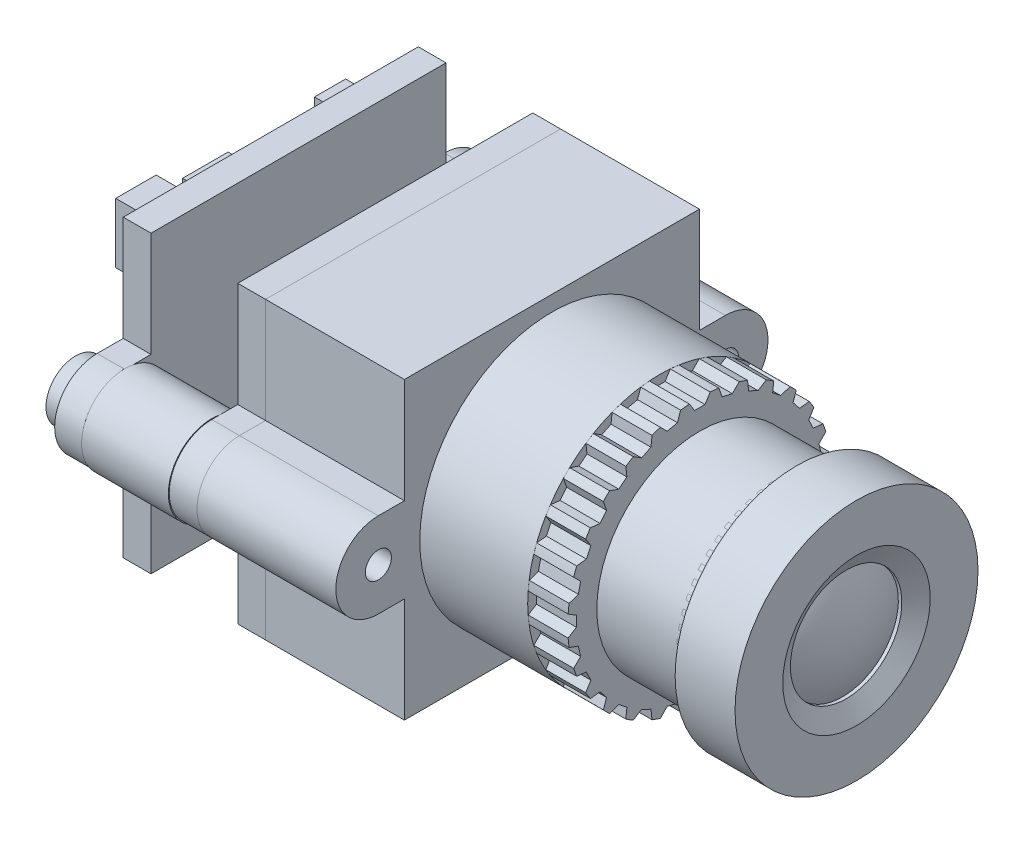
SolidWorks part; units mm, degrees
ref_plane "Front Plane" through (0, 0, 0) normal (0, 0, 1) x (1, 0, 0)
ref_plane "Top Plane" through (0, 0, 0) normal (0, 1, 0) x (1, 0, 0)
ref_plane "Right Plane" through (0, 0, 0) normal (1, 0, 0) x (0, 0, -1)
ref_axis "Axis1" through (-11.8965, 0, 0) along (1, 0, 0)
sketch "Sketch1" plane through (0, 0, 0) normal (1, 0, 0) x (0, 0, -1)
  circle A0 centre (0, 0) radius 7
  dimension "D1" = 14
extrude "Boss-Extrude1" add sketch "Sketch1" against normal blind 3.45
sketch "Sketch2" plane through (-3.45, 0, 0) normal (-1, 0, 0) x (0, 0, 1)
  circle A0 centre (0, 0) radius 5.935
  dimension "D1" = 11.87
extrude "Boss-Extrude2" add sketch "Sketch2" along normal blind 5.58
sketch "Sketch3" plane through (-9.03, 0, 0) normal (-1, 0, 0) x (0, 0, 1)
  circle A0 centre (0, 0) radius 7.61
  dimension "D1" = 15.22
extrude "Boss-Extrude3" add sketch "Sketch3" along normal blind 2.3
sketch "Sketch4" plane through (0, 0, 0) normal (0, 0, 1) x (1, 0, 0)
  line L0 (-3.45, 0) -> (0, 0) construction
  line L1 (-3.45, 5.935) -> (-3.45, -5.935) construction
  line L2 (0, -7) -> (0, 7) construction
  line L3 (0, 7) -> (-3.45, 7) construction
  line L4 (-0.6, 4.25) -> (0, 4.25)
  line L5 (-0.6, 4.25) -> (-0.6, -4.25)
  line L6 (-0.6, -4.25) -> (0, -4.25)
  line L7 (0, 4.25) -> (0, -4.25)
  line L8 (-0.6, 4.25) -> (0, -4.25) construction
  line L9 (-0.6, -4.25) -> (0, 4.25) construction
  line L10 (0, 4.25) -> (-0.6, 3.2108)
  line L11 (-0.8, 0) -> (-0.6, 3.2108) construction
  line L12 (-0.8, -3.2108) -> (-0.6, -3.2108)
  line L13 (-0.8, -3.2108) -> (-0.8, 3.2108)
  line L14 (-0.8, 3.2108) -> (-0.6, 3.2108)
  line L15 (-0.6, -3.2108) -> (-0.6, 3.2108)
  line L16 (-0.8, -3.2108) -> (-0.6, 3.2108) construction
  line L17 (-0.8, 3.2108) -> (-0.6, -3.2108) construction
  line L18 (-0.7, 1.6054) -> (0, 1.6054) construction
  line L19 (-0.8, 0) -> (0, 0)
  line L21 (0, 0) -> (0.6, 0)
  line L22 (0, 0) -> (0, 4.25)
  line L23 (0, 4.25) -> (0.6, 4.25)
  line L24 (0.6, 0) -> (0.6, 4.25)
  spline S0 degree 2 poles (0, 0) (0, 1.7034) (-0.8, 3.2108) knots 0 0 0 1 1 1
  point P6 (-0.3, 0)
  point P15 (-0.7, 0)
  dimension "D1" = 0.6
  dimension "D2" = 2.75
  dimension "D3" = 60
  dimension "D4" = 0.2
  dimension "D5" = 0.6
revolve "Cut-Revolve7" cut sketch "Sketch4" angle 360 about axis through (-11.8965, 0, 0) along (1, 0, 0) region at (0.3, 2.125, 0) region at (-0.2115, 2.72, 0) region at (-0.6658, 3.0768, 0)
sketch "Sketch5" plane through (-9.03, 0, 0) normal (1, 0, 0) x (0, 0, -1)
  line L0 (0, 7.61) -> (0, -7.61) construction
  line L1 (0.6, 7.5863) -> (0.3, 7.11)
  line L2 (0.3, 7.11) -> (-0.3, 7.11)
  line L3 (-0.6, 7.5863) -> (-0.3, 7.11)
  line L4 (2.2731, 7.2626) -> (1.8746, 6.865)
  line L5 (1.8746, 6.865) -> (1.2896, 6.9985)
  line L6 (1.1032, 7.5296) -> (1.2896, 6.9985)
  line L7 (3.8322, 6.5747) -> (3.3552, 6.2757)
  line L8 (3.3552, 6.2757) -> (2.8146, 6.5361)
  line L9 (2.751, 7.0954) -> (2.8146, 6.5361)
  line L10 (5.1991, 5.5571) -> (4.6676, 5.3718)
  line L11 (4.6676, 5.3718) -> (4.1985, 5.7459)
  line L12 (4.2609, 6.3053) -> (4.1985, 5.7459)
  line L13 (6.3053, 4.2609) -> (5.7459, 4.1985)
  line L14 (5.7459, 4.1985) -> (5.3718, 4.6676)
  line L15 (5.5571, 5.1991) -> (5.3718, 4.6676)
  line L16 (7.0954, 2.751) -> (6.5361, 2.8146)
  line L17 (6.5361, 2.8146) -> (6.2757, 3.3552)
  line L18 (6.5747, 3.8322) -> (6.2757, 3.3552)
  line L19 (7.5296, 1.1032) -> (6.9985, 1.2896)
  line L20 (6.9985, 1.2896) -> (6.865, 1.8746)
  line L21 (7.2626, 2.2731) -> (6.865, 1.8746)
  line L22 (7.5863, -0.6) -> (7.11, -0.3)
  line L23 (7.11, -0.3) -> (7.11, 0.3)
  line L24 (7.5863, 0.6) -> (7.11, 0.3)
  line L25 (7.2626, -2.2731) -> (6.865, -1.8746)
  line L26 (6.865, -1.8746) -> (6.9985, -1.2896)
  line L27 (7.5296, -1.1032) -> (6.9985, -1.2896)
  line L28 (6.5747, -3.8322) -> (6.2757, -3.3552)
  line L29 (6.2757, -3.3552) -> (6.5361, -2.8146)
  line L30 (7.0954, -2.751) -> (6.5361, -2.8146)
  line L31 (5.5571, -5.1991) -> (5.3718, -4.6676)
  line L32 (5.3718, -4.6676) -> (5.7459, -4.1985)
  line L33 (6.3053, -4.2609) -> (5.7459, -4.1985)
  line L34 (4.2609, -6.3053) -> (4.1985, -5.7459)
  line L35 (4.1985, -5.7459) -> (4.6676, -5.3718)
  line L36 (5.1991, -5.5571) -> (4.6676, -5.3718)
  line L37 (2.751, -7.0954) -> (2.8146, -6.5361)
  line L38 (2.8146, -6.5361) -> (3.3552, -6.2757)
  line L39 (3.8322, -6.5747) -> (3.3552, -6.2757)
  line L40 (1.1032, -7.5296) -> (1.2896, -6.9985)
  line L41 (1.2896, -6.9985) -> (1.8746, -6.865)
  line L42 (2.2731, -7.2626) -> (1.8746, -6.865)
  line L43 (-0.6, -7.5863) -> (-0.3, -7.11)
  line L44 (-0.3, -7.11) -> (0.3, -7.11)
  line L45 (0.6, -7.5863) -> (0.3, -7.11)
  line L46 (-2.2731, -7.2626) -> (-1.8746, -6.865)
  line L47 (-1.8746, -6.865) -> (-1.2896, -6.9985)
  line L48 (-1.1032, -7.5296) -> (-1.2896, -6.9985)
  line L49 (-3.8322, -6.5747) -> (-3.3552, -6.2757)
  line L50 (-3.3552, -6.2757) -> (-2.8146, -6.5361)
  line L51 (-2.751, -7.0954) -> (-2.8146, -6.5361)
  line L52 (-5.1991, -5.5571) -> (-4.6676, -5.3718)
  line L53 (-4.6676, -5.3718) -> (-4.1985, -5.7459)
  line L54 (-4.2609, -6.3053) -> (-4.1985, -5.7459)
  line L55 (-6.3053, -4.2609) -> (-5.7459, -4.1985)
  line L56 (-5.7459, -4.1985) -> (-5.3718, -4.6676)
  line L57 (-5.5571, -5.1991) -> (-5.3718, -4.6676)
  line L58 (-7.0954, -2.751) -> (-6.5361, -2.8146)
  line L59 (-6.5361, -2.8146) -> (-6.2757, -3.3552)
  line L60 (-6.5747, -3.8322) -> (-6.2757, -3.3552)
  line L61 (-7.5296, -1.1032) -> (-6.9985, -1.2896)
  line L62 (-6.9985, -1.2896) -> (-6.865, -1.8746)
  line L63 (-7.2626, -2.2731) -> (-6.865, -1.8746)
  line L64 (-7.5863, 0.6) -> (-7.11, 0.3)
  line L65 (-7.11, 0.3) -> (-7.11, -0.3)
  line L66 (-7.5863, -0.6) -> (-7.11, -0.3)
  line L67 (-7.2626, 2.2731) -> (-6.865, 1.8746)
  line L68 (-6.865, 1.8746) -> (-6.9985, 1.2896)
  line L69 (-7.5296, 1.1032) -> (-6.9985, 1.2896)
  line L70 (-6.5747, 3.8322) -> (-6.2757, 3.3552)
  line L71 (-6.2757, 3.3552) -> (-6.5361, 2.8146)
  line L72 (-7.0954, 2.751) -> (-6.5361, 2.8146)
  line L73 (-5.5571, 5.1991) -> (-5.3718, 4.6676)
  line L74 (-5.3718, 4.6676) -> (-5.7459, 4.1985)
  line L75 (-6.3053, 4.2609) -> (-5.7459, 4.1985)
  line L76 (-4.2609, 6.3053) -> (-4.1985, 5.7459)
  line L77 (-4.1985, 5.7459) -> (-4.6676, 5.3718)
  line L78 (-5.1991, 5.5571) -> (-4.6676, 5.3718)
  line L79 (-2.751, 7.0954) -> (-2.8146, 6.5361)
  line L80 (-2.8146, 6.5361) -> (-3.3552, 6.2757)
  line L81 (-3.8322, 6.5747) -> (-3.3552, 6.2757)
  line L82 (-1.1032, 7.5296) -> (-1.2896, 6.9985)
  line L83 (-1.2896, 6.9985) -> (-1.8746, 6.865)
  line L84 (-2.2731, 7.2626) -> (-1.8746, 6.865)
  circle A0 centre (0, 0) radius 7.61 construction
  circle A1 centre (0, 0) radius 7.61 construction
  circle A2 centre (0, 0) radius 7.61
  point P12 (0, 7.11)
  point P13 (0, 0)
  point P123 (0, 0)
  circle M6 centre (0, 0) radius 7.61
  dimension "D1" = 0.6
  dimension "D2" = 1.2
  dimension "D3" = 0.5
  dimension "D5" = 0.5063
  dimension "D4" = 28
extrude "Cut-Extrude1" cut sketch "Sketch5" against normal up to next (2.3 mm away) contours L9 L8 L7 M6 | L6 L5 L4 M6 | L0 L2 L1 M6 | L84 L83 L82 M6 | L0 A2 L3 L2 | L81 L80 L79 M6 | L78 L77 L76 M6 | L75 L74 L73 M6 | L72 L71 L70 M6 | L69 L68 L67 M6 | L66 L65 L64 M6 | L63 L62 L61 M6 | L60 L59 L58 M6 | L57 L56 L55 M6 | L51 L50 L49 M6 | L54 L53 L52 M6 | L48 L47 L46 M6 | L0 L44 L43 M6 | L44 L0 A2 L45 | L42 L41 L40 M6 | L39 L38 L37 M6 | L36 L35 L34 M6 | L33 L32 L31 M6 | L30 L29 L28 M6 | L27 L26 L25 M6 | L24 L23 L22 M6 | L21 L20 L19 M6 | L18 L17 L16 M6 | L15 L14 L13 M6 | L12 L11 L10 M6 region at (-9.03, 7.384, -0.233) region at (-9.03, 7.384, 0.233) region at (-9.03, -7.384, -0.233) region at (-9.03, -7.384, 0.233) region at (-9.03, 7.1989, -1.6431) region at (-9.03, 7.1989, 1.6431) region at (-9.03, 6.6527, -3.2038) region at (-9.03, 6.6527, 3.2038) region at (-9.03, -7.1989, 1.6431) region at (-9.03, -7.1989, -1.6431) region at (-9.03, 5.773, -4.6038) region at (-9.03, 5.773, 4.6038) region at (-9.03, -6.6527, 3.2038) region at (-9.03, -6.6527, -3.2038) region at (-9.03, 4.6038, -5.773) region at (-9.03, 4.6038, 5.773) region at (-9.03, -5.773, 4.6038) region at (-9.03, -5.773, -4.6038) region at (-9.03, 3.2038, -6.6527) region at (-9.03, 3.2038, 6.6527) region at (-9.03, -4.6038, 5.773) region at (-9.03, -4.6038, -5.773) region at (-9.03, 1.6431, -7.1989) region at (-9.03, 1.6431, 7.1989) region at (-9.03, -3.2038, 6.6527) region at (-9.03, -3.2038, -6.6527) region at (-9.03, 0, -7.384) region at (-9.03, 0, 7.384) region at (-9.03, -1.6431, 7.1989) region at (-9.03, -1.6431, -7.1989)
sketch "Sketch6" plane through (-11.33, 0, 0) normal (-1, 0, 0) x (0, 0, 1)
  line L0 (0, 7.615) -> (0, -7.615) construction
  line L2 (-8.5, -8.5) -> (8.5, -8.5)
  line L3 (-8.5, -8.5) -> (-8.5, 8.5)
  line L4 (-8.5, 8.5) -> (8.5, 8.5)
  line L5 (8.5, -8.5) -> (8.5, 8.5)
  line L6 (-8.5, -8.5) -> (8.5, 8.5) construction
  line L7 (-8.5, 8.5) -> (8.5, -8.5) construction
  line L8 (-1.25, -7.5117) -> (1.25, -7.5117)
  line L9 (-1.25, -7.5117) -> (-1.25, -8.5)
  line L10 (-1.25, -8.5) -> (1.25, -8.5)
  line L11 (1.25, -7.5117) -> (1.25, -8.5)
  line L12 (-1.25, -7.5117) -> (1.25, -8.5) construction
  line L13 (-1.25, -8.5) -> (1.25, -7.5117) construction
  circle A0 centre (0, 0) radius 7.615
  point P9 (0, -8.0059)
  point P14 (1.54, -7.4577)
  dimension "D1" = 15.23
  dimension "D2" = 17
  dimension "D3" = 2.5
extrude "Boss-Extrude4" add sketch "Sketch6" along normal offset from surface (6.22 mm away) 17.55 contours A0 L9 L2 L11 | A0 region at (-11.33, -8.0398, 0) up to face at (0, 0, 4.25)
sketch "Sketch7" plane through (-17.55, 0, 0) normal (-1, 0, 0) x (0, 0, 1)
  line L0 (1.25, -8.5) -> (-1.25, -8.5) construction
  line L1 (-8.5, -8.5) -> (8.5, -8.5)
  line L2 (-8.5, -8.5) -> (-8.5, 8.5)
  line L3 (-8.5, 8.5) -> (8.5, 8.5)
  line L4 (8.5, -8.5) -> (8.5, 8.5)
  line L5 (-8.5, -8.5) -> (8.5, 8.5) construction
  line L6 (-8.5, 8.5) -> (8.5, -8.5) construction
  line L7 (-8.5, 0) -> (8.5, 0) construction
  line L8 (0, 8.5) -> (0, -8.5) construction
  line L9 (-10, 2.45) -> (-8.5, 2.45)
  line L10 (-10, -2.45) -> (-8.5, -2.45)
  line L11 (10, 2.45) -> (8.5, 2.45)
  line L12 (10, -2.45) -> (8.5, -2.45)
  circle A0 centre (-10, 0) radius 2.45
  circle A1 centre (-10, 0) radius 0.75
  circle A2 centre (10, 0) radius 0.75
  circle A3 centre (10, 0) radius 2.45
  point P0 (0, 0)
  dimension "D1" = 4.9
  dimension "D3" = 1.5
  dimension "D2" = 20
extrude "Boss-Extrude5" add sketch "Sketch7" along normal blind 8 contours A0 L10 L2 | L2 A0 A1 | A0 L2 L9 | L12 A3 L4 | A3 L4 A2 | L4 A3 L11 | L1 L4 L3 L2 region at (-17.55, -2.2994, -8.8667) region at (-17.55, -2.2994, 8.8667) region at (-17.55, -2.2587, -9.2277) region at (-17.55, 0, 8.5629) region at (-17.55, 2.2994, -8.8667) region at (-17.55, 2.2994, 8.8667)
sketch "Sketch8" plane through (-25.55, 0, 0) normal (-1, 0, 0) x (0, 0, 1)
  line L10 (-10, -2.45) -> (-8.5, -2.45)
  line L11 (-8.5, -2.45) -> (-8.5, -8.5)
  line L12 (-8.5, -8.5) -> (8.5, -8.5)
  line L13 (8.5, -8.5) -> (8.5, -2.45)
  line L14 (8.5, -2.45) -> (10, -2.45)
  line L15 (10, 2.45) -> (8.5, 2.45)
  line L16 (8.5, 2.45) -> (8.5, 8.5)
  line L17 (8.5, 8.5) -> (-8.5, 8.5)
  line L18 (-8.5, 8.5) -> (-8.5, 2.45)
  line L19 (-8.5, 2.45) -> (-10, 2.45)
  line L20 (-10, -2.45) -> (-8.5, -2.45)
  line L21 (-8.5, -2.45) -> (-8.5, -8.5)
  line L22 (-8.5, -8.5) -> (8.5, -8.5)
  line L23 (8.5, -8.5) -> (8.5, -2.45)
  line L24 (8.5, -2.45) -> (10, -2.45)
  line L25 (10, 2.45) -> (8.5, 2.45)
  line L26 (8.5, 2.45) -> (8.5, 8.5)
  line L27 (8.5, 8.5) -> (-8.5, 8.5)
  line L28 (-8.5, 8.5) -> (-8.5, 2.45)
  line L29 (-8.5, 2.45) -> (-10, 2.45)
  circle A0 centre (10, 0) radius 0.75 construction
  circle A1 centre (-10, 0) radius 0.75 construction
  arc A2 (10, -2.45) -> (10, 2.45) centre (10, 0) ccw
  arc A3 (-10, 2.45) -> (-10, -2.45) centre (-10, 0) ccw
  arc A4 (10, -2.45) -> (10, 2.45) centre (10, 0) ccw
  arc A5 (-10, 2.45) -> (-10, -2.45) centre (-10, 0) ccw
  circle A6 centre (10, 0) radius 0.75
  circle A7 centre (-10, 0) radius 0.75
  dimension "D1" = 0
extrude "Boss-Extrude6" add sketch "Sketch8" along normal blind 1.6 separate body
sketch "Sketch9" plane through (-27.15, 0, 0) normal (-1, 0, 0) x (0, 0, 1)
  line L0 (0, 8.5) -> (0, -8.5) construction
  line L1 (8.5, 8.5) -> (-8.5, 8.5) construction
  line L2 (-8.5, -8.5) -> (8.5, -8.5) construction
  circle A0 centre (-10, 0) radius 2.5
  circle A1 centre (-10, 0) radius 1
  circle A2 centre (10, 0) radius 2.5
  circle A3 centre (10, 0) radius 1
  dimension "D1" = 5
  dimension "D2" = 2
extrude "Boss-Extrude7" add sketch "Sketch9" along normal blind 5 separate body
sketch "Sketch10" plane through (-32.15, 0, 0) normal (-1, 0, 0) x (0, 0, 1)
  line L10 (-10, -2.45) -> (-8.5, -2.45)
  line L11 (-8.5, -2.45) -> (-8.5, -8.5)
  line L12 (-8.5, -8.5) -> (8.5, -8.5)
  line L13 (8.5, -8.5) -> (8.5, -2.45)
  line L14 (8.5, -2.45) -> (10, -2.45)
  line L15 (10, 2.45) -> (8.5, 2.45)
  line L16 (8.5, 2.45) -> (8.5, 8.5)
  line L17 (8.5, 8.5) -> (-8.5, 8.5)
  line L18 (-8.5, 8.5) -> (-8.5, 2.45)
  line L19 (-8.5, 2.45) -> (-10, 2.45)
  line L20 (-10, -2.45) -> (-8.5, -2.45)
  line L21 (-8.5, -2.45) -> (-8.5, -8.5)
  line L22 (-8.5, -8.5) -> (8.5, -8.5)
  line L23 (8.5, -8.5) -> (8.5, -2.45)
  line L24 (8.5, -2.45) -> (10, -2.45)
  line L25 (10, 2.45) -> (8.5, 2.45)
  line L26 (8.5, 2.45) -> (8.5, 8.5)
  line L27 (8.5, 8.5) -> (-8.5, 8.5)
  line L28 (-8.5, 8.5) -> (-8.5, 2.45)
  line L29 (-8.5, 2.45) -> (-10, 2.45)
  circle A0 centre (-10, 0) radius 0.75 construction
  circle A1 centre (10, 0) radius 0.75 construction
  arc A2 (-10, 2.45) -> (-10, -2.45) centre (-10, 0) ccw
  arc A3 (10, -2.45) -> (10, 2.45) centre (10, 0) ccw
  arc A4 (-10, 2.45) -> (-10, -2.45) centre (-10, 0) ccw
  arc A5 (10, -2.45) -> (10, 2.45) centre (10, 0) ccw
  circle A6 centre (10, 0) radius 0.75
  circle A7 centre (-10, 0) radius 0.75
  dimension "D1" = 0
extrude "Boss-Extrude8" add sketch "Sketch10" along normal blind 1.6 separate body
sketch "Sketch11" plane through (-33.75, 0, 0) normal (-1, 0, 0) x (0, 0, 1)
  line L0 (0, 8.5) -> (0, -8.5) construction
  line L1 (8.5, 8.5) -> (-8.5, 8.5) construction
  line L2 (-8.5, -8.5) -> (8.5, -8.5) construction
  line L4 (-3.5, -4.7) -> (3.5, -4.7)
  line L5 (-3.5, -4.7) -> (-3.5, -7.9)
  line L6 (-3.5, -7.9) -> (3.5, -7.9)
  line L7 (3.5, -4.7) -> (3.5, -7.9)
  line L8 (-3.5, -4.7) -> (3.5, -7.9) construction
  line L9 (-3.5, -7.9) -> (3.5, -4.7) construction
  point P6 (0, -6.3)
  dimension "D1" = 7
  dimension "D2" = 3.2
  dimension "D3" = 0.6
extrude "Boss-Extrude9" add sketch "Sketch11" along normal blind 4.8 separate body
sketch "Sketch12" plane through (-38.55, 0, 0) normal (-1, 0, 0) x (0, 0, 1)
  line L0 (-3.5, -4.7) -> (3.5, -7.9) construction
  line L1 (3.5, -7.9) -> (3.5, -4.7) construction
  line L2 (-3.15, -7.55) -> (3.15, -7.55)
  line L3 (-3.15, -7.55) -> (-3.15, -5.05)
  line L4 (-3.15, -5.05) -> (3.15, -5.05)
  line L5 (3.15, -7.55) -> (3.15, -5.05)
  line L6 (-3.15, -7.55) -> (3.15, -5.05) construction
  line L7 (-3.15, -5.05) -> (3.15, -7.55) construction
  line L8 (3.15, -5.05) -> (3.5, -5.05) construction
  line L9 (3.15, -5.05) -> (3.15, -4.7) construction
  line L10 (3.5, -4.7) -> (-3.5, -4.7) construction
  point P4 (0, -6.3)
  dimension "D1" = 0.35
extrude "Cut-Extrude2" cut sketch "Sketch12" against normal offset from surface (4.4 mm away) 0.4 up to face at (-33.75, 0, 10.75)
sketch "Sketch13" plane through (-38.55, 0, 0) normal (-1, 0, 0) x (0, 0, 1)
  line L0 (0, -5.05) -> (0, -4.7) construction
  line L1 (3.15, -5.05) -> (-3.15, -5.05) construction
  line L2 (3.5, -4.7) -> (-3.5, -4.7) construction
  line L4 (-2.4, -5.05) -> (2.4, -5.05)
  line L5 (-2.4, -5.05) -> (-2.4, -4.7)
  line L6 (-2.4, -4.7) -> (2.4, -4.7)
  line L7 (2.4, -5.05) -> (2.4, -4.7)
  line L8 (-2.4, -5.05) -> (2.4, -4.7) construction
  line L9 (-2.4, -4.7) -> (2.4, -5.05) construction
  point P6 (0, -4.875)
  dimension "D1" = 4.8
extrude "Cut-Extrude3" cut sketch "Sketch13" against normal blind 1.5
sketch "Sketch14" plane through (-33.75, 0, 0) normal (-1, 0, 0) x (0, 0, 1)
  line L1 (6.733, 7.4544) -> (4.4023, 7.4544)
  line L2 (6.733, 7.4544) -> (6.733, 3.9954)
  line L3 (6.733, 3.9954) -> (4.4023, 3.9954)
  line L4 (4.4023, 7.4544) -> (4.4023, 3.9954)
  line L5 (3.6255, -8.0463) -> (5.9191, -8.0463)
  line L6 (3.6255, -8.0463) -> (3.6255, -4.1064)
  line L7 (3.6255, -4.1064) -> (5.9191, -4.1064)
  line L8 (5.9191, -8.0463) -> (5.9191, -4.1064)
  line L9 (-2.5526, -1.9607) -> (-0.9249, -1.9607)
  line L10 (-2.5526, -1.9607) -> (-2.5526, -3.8844)
  line L11 (-2.5526, -3.8844) -> (-0.9249, -3.8844)
  line L12 (-0.9249, -1.9607) -> (-0.9249, -3.8844)
  line L13 (-3.4035, 2.1827) -> (0.8694, 2.1827)
  line L14 (-3.4035, 2.1827) -> (-3.4035, 0.222)
  line L15 (-3.4035, 0.222) -> (0.8694, 0.222)
  line L16 (0.8694, 2.1827) -> (0.8694, 0.222)
  line L17 (-6.511, 6.7885) -> (-4.7168, 6.7885)
  line L18 (-6.511, 6.7885) -> (-6.511, 3.9954)
  line L19 (-6.511, 3.9954) -> (-4.7168, 3.9954)
  line L20 (-4.7168, 6.7885) -> (-4.7168, 3.9954)
  line L21 (0.259, 6.5295) -> (2.8856, 6.5295)
  line L22 (0.259, 6.5295) -> (0.259, 5.1977)
  line L23 (0.259, 5.1977) -> (2.8856, 5.1977)
  line L24 (2.8856, 6.5295) -> (2.8856, 5.1977)
extrude "Boss-Extrude10" add sketch "Sketch14" along normal blind 2.2
sketch "Sketch15" plane through (-33.75, 0, 0) normal (-1, 0, 0) x (0, 0, 1)
  circle A0 centre (-10, 0) radius 1.7
  circle A1 centre (10, 0) radius 1.7
  dimension "D1" = 3.4
extrude "Boss-Extrude11" add sketch "Sketch15" along normal blind 1.25
sketch "Sketch16" plane through (-3.45, 0, 0) normal (-1, 0, 0) x (0, 0, 1)
  circle A0 centre (0, 0) radius 5.935 construction
  circle A1 centre (0, 0) radius 5.935
extrude "Boss-Extrude12" add sketch "Sketch16" along normal blind 1 separate body
ref_axis "Axis2" through (-40.4775, 0, 0) along (1, 0, 0)
ref_plane "Plane1" through (10, 0, 0) normal (1, 0, 0) x (0, 0, -1)
ref_plane "Plane2" through (-3.45, 0, 0) normal (-1, 0, 0) x (0, 0, 1)
ref_point "Camera position"
ref_point "Camera target"
